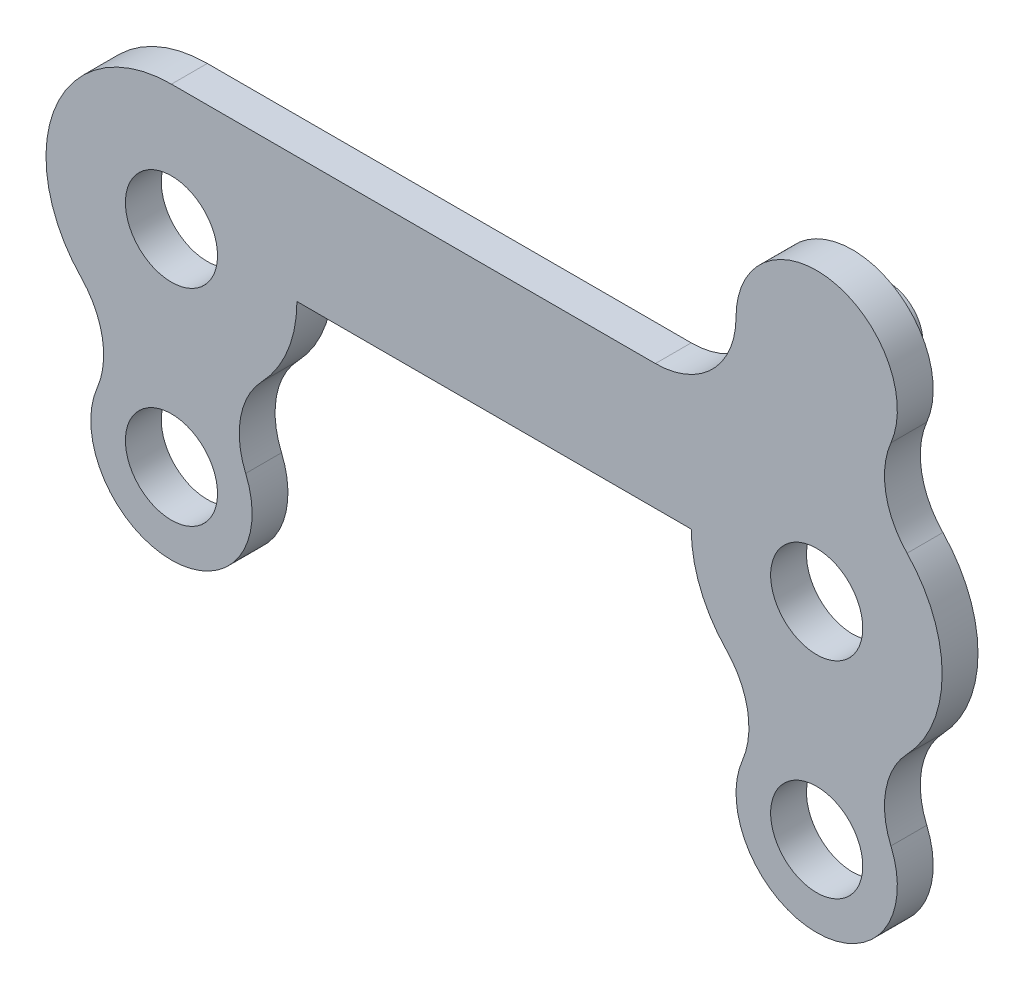
SolidWorks part; units mm, degrees
material "ABS"
ref_plane "Front Plane" through (0, 0, 0) normal (0, 0, 1) x (1, 0, 0)
ref_plane "Top Plane" through (0, 0, 0) normal (0, 1, 0) x (1, 0, 0)
ref_plane "Right Plane" through (0, 0, 0) normal (1, 0, 0) x (0, 0, -1)
sketch "Sketch1" plane through (0, 0, 0) normal (0, 0, 1) x (1, 0, 0)
  line L0 (5.5562, 0) -> (23.0188, 0)
  line L1 (0, 5.5562) -> (28.575, 5.5562)
  line L5 (0, 5.5562) -> (28.575, 5.5562) construction
  circle A0 centre (0, 0) radius 5.5562 construction
  circle A1 centre (28.575, 0) radius 5.5562 construction
  arc A2 (0, 5.5562) -> (0, -5.5562) centre (0, 0) ccw
  arc A3 (28.575, -5.5562) -> (28.575, 5.5562) centre (28.575, 0) ccw
  circle A4 centre (0, 0) radius 1.7859
  circle A5 centre (28.575, 0) radius 1.7859
  arc A6 (0, -5.5562) -> (5.5562, 0) centre (0, 0) ccw
  arc A7 (23.0188, 0) -> (28.575, -5.5562) centre (28.575, 0) ccw
  circle A10 centre (0, -9.1281) radius 3.5719
  circle A12 centre (28.575, -9.1281) radius 1.7859
  circle A15 centre (0, -9.1281) radius 1.7859
  circle A17 centre (28.575, -9.1281) radius 3.5719
  circle A27 centre (-6.5741, -6.3327) radius 3.5719
  circle A28 centre (6.5741, -6.3327) radius 3.5719
  circle A29 centre (22.0009, -6.3327) radius 3.5719
  circle A30 centre (35.1491, -6.3327) radius 3.5719
  circle A31 centre (28.575, 9.1281) radius 1.7859
  circle A32 centre (28.575, 9.1281) radius 3.5719
  circle A33 centre (21.4313, 9.1281) radius 3.5719
  circle A34 centre (35.1491, 6.3327) radius 3.5719
  dimension "D1" = 28.575
  dimension "D2" = 11.1125
  dimension "D3" = 3.5719
  dimension "D6" = 7.1437
  dimension "D7" = 3.5719
sketch "Sketch2" plane through (0, 0, 0) normal (0, 0, 1) x (1, 0, 0)
  line L0 (5.5562, 0) -> (23.0188, 0)
  line L2 (0, 5.5562) -> (28.575, 5.5562)
  circle A0 centre (0, 0) radius 5.5562
  circle A1 centre (28.575, 0) radius 5.5563
  circle A2 centre (28.575, -9.1281) radius 3.5719
  circle A3 centre (0, -9.1281) radius 3.5719
  circle A4 centre (6.5741, -6.3327) radius 3.5719
  circle A5 centre (-6.5741, -6.3327) radius 3.5719
  circle A6 centre (22.0009, -6.3327) radius 3.5719
  circle A7 centre (35.1491, -6.3327) radius 3.5719
  circle A8 centre (28.575, 9.1281) radius 3.5719
  arc A9 (0, -5.5562) -> (5.5562, 0) centre (0, 0) ccw construction
  arc A10 (23.0188, 0) -> (28.575, -5.5562) centre (28.575, 0) ccw construction
  circle A11 centre (28.575, -9.1281) radius 3.5719 construction
  circle A12 centre (0, -9.1281) radius 3.5719 construction
  circle A13 centre (22.0009, -6.3327) radius 3.5719 construction
  circle A15 centre (28.575, 9.1281) radius 3.5719 construction
  circle A16 centre (35.1491, 6.3327) radius 3.5719
  circle A18 centre (35.1491, 6.3327) radius 3.5719 construction
  circle A19 centre (0, 0) radius 2.0399
  circle A20 centre (28.575, 0) radius 2.0399
  circle A21 centre (0, -9.1281) radius 2.0399
  circle A22 centre (28.575, -9.1281) radius 2.0399
  circle A28 centre (28.575, 9.1281) radius 1.5319
  circle A30 centre (21.4313, 9.1281) radius 3.5719
  circle A31 centre (21.4313, 9.1281) radius 3.5719 construction
  dimension "D1" = 4.0799
  dimension "D2" = 4.0799
  dimension "D3" = 3.0639
extrude "Boss-Extrude1" add sketch "Sketch2" along normal blind 1.5875 contours A0 A19 | A5 A3 A0 | A4 A0 A3 | A3 A21 | A2 A22 | A6 A2 A1 | A7 A1 A2 | A1 A20 | A1 L2 A0 L0 | A30 L2 A8 | A16 A8 A1 | A8 A28 region at (14.2875, 2.9628, 0) region at (5.0072, -2.0194, 0) region at (24.7573, 3.8177, 0) region at (2.4105, -5.669, 0) region at (30.9855, 5.669, 0) region at (25.0031, 6.3541, 0) region at (26.1207, 6.6739, 0) region at (26.1645, -5.669, 0) region at (-2.4105, -5.669, 0) region at (1.9148, -6.2332, 0) region at (30.9855, -5.669, 0) region at (30.4898, -6.2332, 0)
extrude "Boss-Extrude3" add sketch "Sketch2<4>" along normal blind 1.5875 and the other way blind 1.5875 contours A28 region at (28.575, 9.1281, 0)
sketch "Sketch2<4>" plane through (0, 0, 0) normal (0, 0, 1) x (1, 0, 0) same geometry as "Sketch2"
